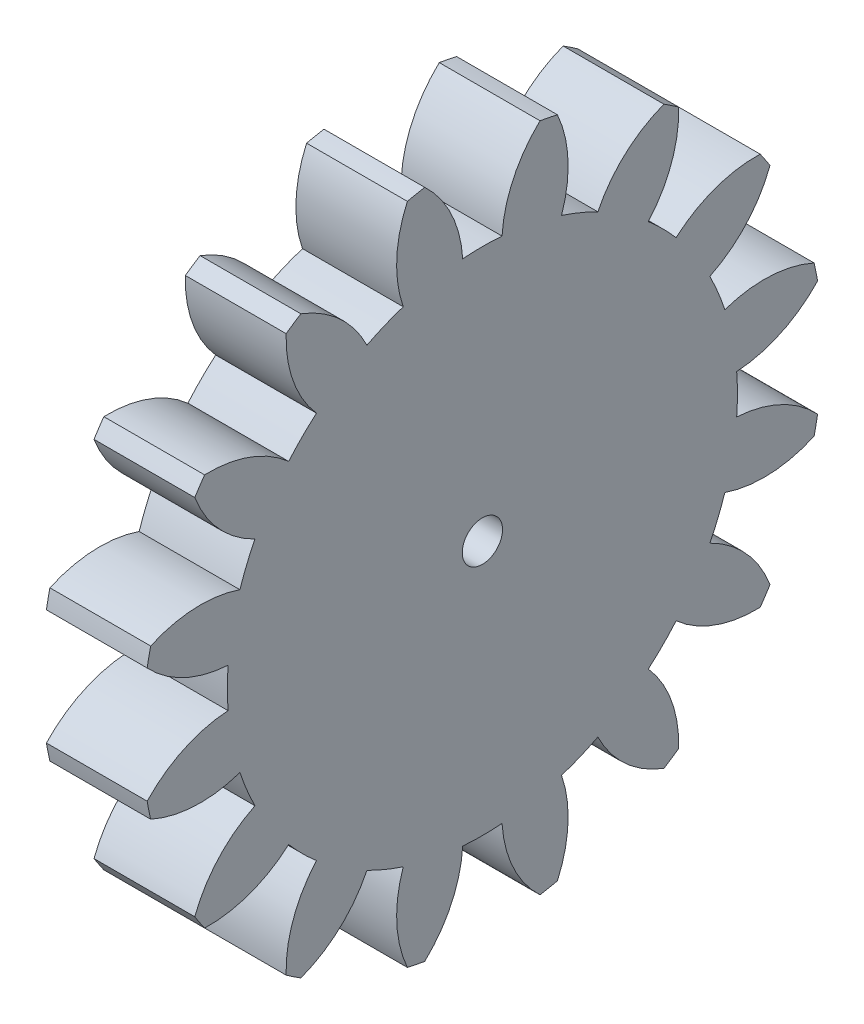
SolidWorks part; units mm, degrees
ref_plane "Plane1" through (0, 0, 0) normal (0, 0, 1) x (1, 0, 0)
ref_plane "Plane2" through (0, 0, 0) normal (0, 1, 0) x (1, 0, 0)
ref_plane "Plane3" through (0, 0, 0) normal (1, 0, 0) x (0, 0, -1)
sketch "HoldingSke" plane through (0, 0, 0) normal (0, 1, 0) x (1, 0, 0)
  line L0 (0, 0) -> (0.3204, -0.0919)
  line L1 (-15, 0) -> (100, 0) construction
  line L2 (0, 0) -> (-2.1039, 2.3779)
  line L3 (0, 0) -> (-11.863, 4.5341)
  line L4 (0, 0) -> (8.3015, 2.3804)
  line L5 (0, 0) -> (-46.8476, -17.4728)
  line L6 (0, 0) -> (-6.6317, -4.4744)
  line L7 (-2.1039, 2.3779) -> (8.6586, 51.2059)
  line L8 (-76.2, 54.61) -> (-76.1, 54.61)
  line L9 (-71.009, 38.7566) -> (-53.1078, 45.2721)
  line L10 (-76.2, 71.12) -> (104.1128, 71.12)
  line L11 (0, 0) -> (-8, 0)
  line L12 (-76.2, 101.6) -> (-76.093, 101.6)
  line L13 (24.9733, 27.94) -> (52.9518, 28.4284)
  line L14 (24.9733, 27.94) -> (24.9743, 27.94)
  line L15 (24.9733, 27.94) -> (100.4006, 29.5858)
  line L16 (-63.627, -3) -> (-12.827, -3)
  circle A0 centre (0, 0) radius 0.4
  circle A1 centre (0, 0) radius 20.249
  circle A2 centre (0, 0) radius 37.5
  circle A3 centre (0, 0) radius 0.4
  dimension "MHD" = 40.498
  dimension "Hub_dia" = 75
  dimension "Bore" = 0.8
  dimension "MBD" = 0.8
  dimension "Num_teeth" = 16
  dimension "Pitch" = 0.3333
  dimension "Overall_len" = 50
  dimension "Show_teeth" = 16
  dimension "Thickness" = 8
  dimension "OAL" = 50.0001
  dimension "T_dim" = 0.1
  dimension "Ap" = 20
  dimension "H" = 19.05
  dimension "Pitch_radius" = 180.3128
  dimension "Width" = 8
  dimension "Backlash" = 0.107
  dimension "Addendum_fac" = 1
  dimension "Dedendum_fac" = 1.25
  dimension "Clearance_fac" = 0.25
  dimension "Dedendum_add" = 0.001
  dimension "Module" = 3
sketch "BasProSke" plane through (0, 0, 0) normal (0, 1, 0) x (1, 0, 0)
  line L0 (-10, 0) -> (60, 0) construction
  line L1 (0, 0) -> (0, 27)
  line L2 (0, 0) -> (8, 0)
  line L3 (8, 0) -> (8, 27)
  line L4 (8, 27) -> (0, 27)
  dimension "Thickness" = 8
  dimension "Diameter" = 54
revolve "Base-Revolve" add sketch "BasProSke" angle 360 about L0
sketch "TooCutSke" plane through (0, 0, 0) normal (1, 0, 0) x (0, 0, -1)
  line L1 (0, 0) -> (0, 107) construction
  line L2 (0, 0) -> (-2.5395, 23.8653) construction
  line L3 (0, 0) -> (-9.3262, 46.8857) construction
  line L4 (-2.5395, 23.8653) -> (-4.6631, 23.4429) construction
  arc A0 (1.5612, 20.1887) -> (-1.5612, 20.1887) centre (0, 0) ccw
  arc A1 (4.5995, 26.6311) -> (-4.5995, 26.6311) centre (0, 0) ccw
  circle A2 centre (0, 0) radius 24 construction
  circle A3 centre (0, 0) radius 22.5526 construction
  arc A4 (-1.5612, 20.1887) -> (-4.5995, 26.6311) centre (-11.1435, 19.6072) ccw
  arc A5 (4.5995, 26.6311) -> (1.5612, 20.1887) centre (11.1435, 19.6072) ccw
  dimension "Root_dia" = 40.498
  dimension "Overcut_dia" = 54.0508
  dimension "Pitch_dia" = 48
  dimension "Base_dia" = 45.1052
  dimension "Flank_rad" = 9.6
  dimension "Half_ang" = 11.25
  dimension "Half_CT" = 2.1652
extrude "ToothCut" cut sketch "TooCutSke" along normal through all
fillet "Breaks" [suppressed] radius 0.06 tangent propagation no
fillet "RootFillets" [suppressed] radius 0.751
pattern_circular "TeethCuts" count 16 every 22.5 about axis through (-10, 0, 0) along (1, 0, 0) of "ToothCut", "RootFillets", "Breaks"
sketch "HubNeaOneSke" plane through (0, 0, 0) normal (-1, 0, 0) x (0, 0, 1)
  circle A0 centre (0, 0) radius 20.249
  dimension "Diameter" = 40.498
extrude "HubNearOne" [suppressed] add sketch "HubNeaOneSke" along normal blind 42.0001
sketch "HubNeaBotSke" plane through (0, 0, 0) normal (-1, 0, 0) x (0, 0, 1)
  circle A0 centre (0, 0) radius 20.249
  dimension "Diameter" = 40.498
extrude "HubNearBoth" [suppressed] add sketch "HubNeaBotSke" along normal blind 21
ref_plane "FarPln" through (8, 0, 0) normal (1, 0, 0) x (0, 0, -1)
sketch "HubFarSke" plane through (8, 0, 0) normal (1, 0, 0) x (0, 0, -1)
  circle A0 centre (0, 0) radius 20.249
  dimension "Diameter" = 40.498
extrude "HubFar" [suppressed] add sketch "HubFarSke" along normal blind 21
sketch "BorSke" plane through (0, 0, 0) normal (1, 0, 0) x (0, 0, -1)
  circle A0 centre (0, 0) radius 0.4
  dimension "Diameter" = 0.8
extrude "Bore" cut sketch "BorSke" along normal mid plane 100.0001
sketch "KeySke" plane through (0, 0, 0) normal (1, 0, 0) x (0, 0, -1)
  line L0 (-0.05, 0) -> (-0.05, 0.5)
  line L1 (-0.05, 0.5) -> (0.05, 0.5)
  line L2 (0.05, 0.5) -> (0.05, 0)
  line L3 (0, 0) -> (0, 34) construction
  line L4 (-0.05, 0) -> (0.05, 0)
  dimension "Offset" = 0.5
  dimension "Width" = 0.1
extrude "Keyway" [suppressed] cut sketch "KeySke" along normal mid plane 100.0001
pattern_circular "Keyway2" [suppressed] count 2 every 90 about axis through (-10, 0, 0) along (1, 0, 0) reverse direction yes
sketch "草图1" plane through (8, 0, 0) normal (1, 0, 0) x (0, 0, -1)
  circle A0 centre (0, 0) radius 1.6
  dimension "D1" = 3.2
extrude "切除-拉伸1" cut sketch "草图1" against normal blind 10
ref_axis "基准轴1" through (0, 0, 0) along (1, 0, 0)
equation "' \"Module@HoldingSke\" = 6.35"
equation "' \"Num_teeth@HoldingSke\" = 12"
equation "' \"Ap@HoldingSke\" =  20"
equation "' \"Ap@HoldingSke\" = 20"
equation "' \"Width@HoldingSke\" = 0.5 * 25.4"
equation "' \"Hub_dia@HoldingSke\"= 1 * 25.4"
equation "' \"Hub_dia@HoldingSke\" = 1 * 25.4"
equation "' \"Overall_len@HoldingSke\" = 1.0 * 25.4"
equation "' \"Bore@HoldingSke\" = 0.75 * 25.4"
equation "' \"T_dim@HoldingSke\" = 0.1 * 25.4"
equation "' \"Width@KeySke\" = 0.25 * 25.4"
equation "' \"Show_teeth@HoldingSke\" = 13"
equation "' \"Backlash@HoldingSke\" = 0.009 * 25.4"
equation "' \"Addendum_fac@HoldingSke\" = 1.0"
equation "' \"Dedendum_fac@HoldingSke\" = 1.25"
equation "' \"Dedendum_add@HoldingSke\" = 0.00005 * 25.4"
equation "' \"Clearance_fac@HoldingSke\" = 0.25"
equation "\"Pitch@HoldingSke\" = 1 / \"Module@HoldingSke\""
equation "\"Overcut_dia@TooCutSke\" = (\"Num_teeth@HoldingSke\" + 2 * \"Addendum_fac@HoldingSke\") / \"Pitch@HoldingSke\" + 0.002 * 25.4"
equation "\"Pitch_dia@TooCutSke\" = \"Num_teeth@HoldingSke\" / \"Pitch@HoldingSke\""
equation "\"Base_dia@TooCutSke\" = \"Num_teeth@HoldingSke\" / \"Pitch@HoldingSke\" * cos((\"Ap@HoldingSke\"  * 3.14159265 / 180))"
equation "\"Root_dia@TooCutSke\" = (\"Num_teeth@HoldingSke\" + 2) / \"Pitch@HoldingSke\" - 2 * (\"Addendum_fac@HoldingSke\" + \"Dedendum_fac@HoldingSke\") / \"Pitch@HoldingSke\" - \"Dedendum_add@HoldingSke\" * 2"
equation "\"Half_ang@TooCutSke\" = 180 / \"Num_teeth@HoldingSke\""
equation "\"Half_CT@TooCutSke\" = \"Num_teeth@HoldingSke\" / \"Pitch@HoldingSke\" * sin((3.14159265 / 2 / \"Num_teeth@HoldingSke\")) / 2 - 7 * \"Backlash@HoldingSke\" / 4"
equation "\"Flank_rad@TooCutSke\" = \"Num_teeth@HoldingSke\" / \"Pitch@HoldingSke\" / 5"
equation "\"Radius@RootFillets\" = \"Clearance_fac@HoldingSke\" / \"Pitch@HoldingSke\" + \"Dedendum_add@HoldingSke\""
equation "\"Break_rad@Breaks\" = 0.02 / \"Pitch@HoldingSke\""
equation "\"Thickness@HoldingSke\" = \"Width@HoldingSke\""
equation "\"OAL@HoldingSke\" = \"Thickness@HoldingSke\""
equation "\"MHD@HoldingSke\" = (\"Num_teeth@HoldingSke\" + 2) / \"Pitch@HoldingSke\" - 2 * (\"Addendum_fac@HoldingSke\" + \"Dedendum_fac@HoldingSke\")  / \"Pitch@HoldingSke\" - \"Dedendum_add@HoldingSke\" * 2"
equation "\"MBD@HoldingSke\" = (\"Num_teeth@HoldingSke\" + 2) / \"Pitch@HoldingSke\" - 2 * (\"Addendum_fac@HoldingSke\" + \"Dedendum_fac@HoldingSke\")  / \"Pitch@HoldingSke\" - \"Dedendum_add@HoldingSke\" * 2 - 0.002 * 25.4"
equation "\"MHD@HoldingSke\" = ((sgn( \"MHD@HoldingSke\" - \"Hub_dia@HoldingSke\" )-1)*( \"MHD@HoldingSke\" - \"Hub_dia@HoldingSke\" ))/-2+ \"Hub_dia@HoldingSke\""
equation "\"MBD@HoldingSke\" = ((sgn( \"MBD@HoldingSke\" - \"Bore@HoldingSke\" )-1)*( \"MBD@HoldingSke\" - \"Bore@HoldingSke\" ))/-2+ \"Bore@HoldingSke\""
equation "\"OAL@HoldingSke\" = ((sgn( \"OAL@HoldingSke\" - \"Overall_len@HoldingSke\" )+1)*( \"OAL@HoldingSke\" - \"Overall_len@HoldingSke\" ))/2 + \"Overall_len@HoldingSke\" + 0.000002 * 25.4"
equation "\"Num_teeth@TeethCuts\" = int( \"Show_teeth@HoldingSke\" ) + 1"
equation "\"Num_teeth@TeethCuts\" = ((sgn( \"Num_teeth@TeethCuts\" - \"Num_teeth@HoldingSke\" )-1)*( \"Num_teeth@TeethCuts\" - \"Num_teeth@HoldingSke\" ))/-2+ \"Num_teeth@HoldingSke\""
equation "\"Num_teeth@TeethCuts\" = ((sgn( \"Num_teeth@TeethCuts\" - 2.0)+1)*( \"Num_teeth@TeethCuts\" - 2.0))/2 +2.0"
equation "\"Angle@TeethCuts\" = 360.0 / \"Num_teeth@HoldingSke\""
equation "\"Diameter@BasProSke\" = (\"Num_teeth@HoldingSke\" + 2 * \"Addendum_fac@HoldingSke\") / \"Pitch@HoldingSke\""
equation "\"Thickness@BasProSke\"  = \"Thickness@HoldingSke\""
equation "' \"Fillet_rad@BasProSke\" =  \"Thickness@HoldingSke\" * 0.05"
equation "' \"Fillet_rad@BasProSke\" = \"Thickness@HoldingSke\" * 0.05"
equation "\"MHD@HoldingSke\" = ((sgn( \"MHD@HoldingSke\" - \"Root_dia@TooCutSke\" )-1)*( \"MHD@HoldingSke\" - \"Root_dia@TooCutSke\" ))/-2+ \"Root_dia@TooCutSke\""
equation "\"Diameter@HubNeaOneSke\" = \"MHD@HoldingSke\""
equation "\"Length@HubNearOne\" = \"OAL@HoldingSke\" - \"Thickness@BasProSke\""
equation "\"Diameter@HubNeaBotSke\" = \"MHD@HoldingSke\""
equation "\"Length@HubNearBoth\" = ( \"OAL@HoldingSke\" - \"Thickness@BasProSke\" ) / 2.0"
equation "\"Thickness@FarPln\" = \"Thickness@BasProSke\""
equation "\"Diameter@HubFarSke\" = \"MHD@HoldingSke\""
equation "\"Length@HubFar\" = ( \"OAL@HoldingSke\" - \"Thickness@BasProSke\" ) / 2.0"
equation "\"Diameter@BorSke\" = \"MBD@HoldingSke\""
equation "\"D1@Bore\" = \"OAL@HoldingSke\" * 2.0"
equation "\"D1@Keyway\" = \"OAL@HoldingSke\" * 2.0"
equation "\"Offset@KeySke\" = \"T_dim@HoldingSke\" + \"MBD@HoldingSke\" / 2.0"
